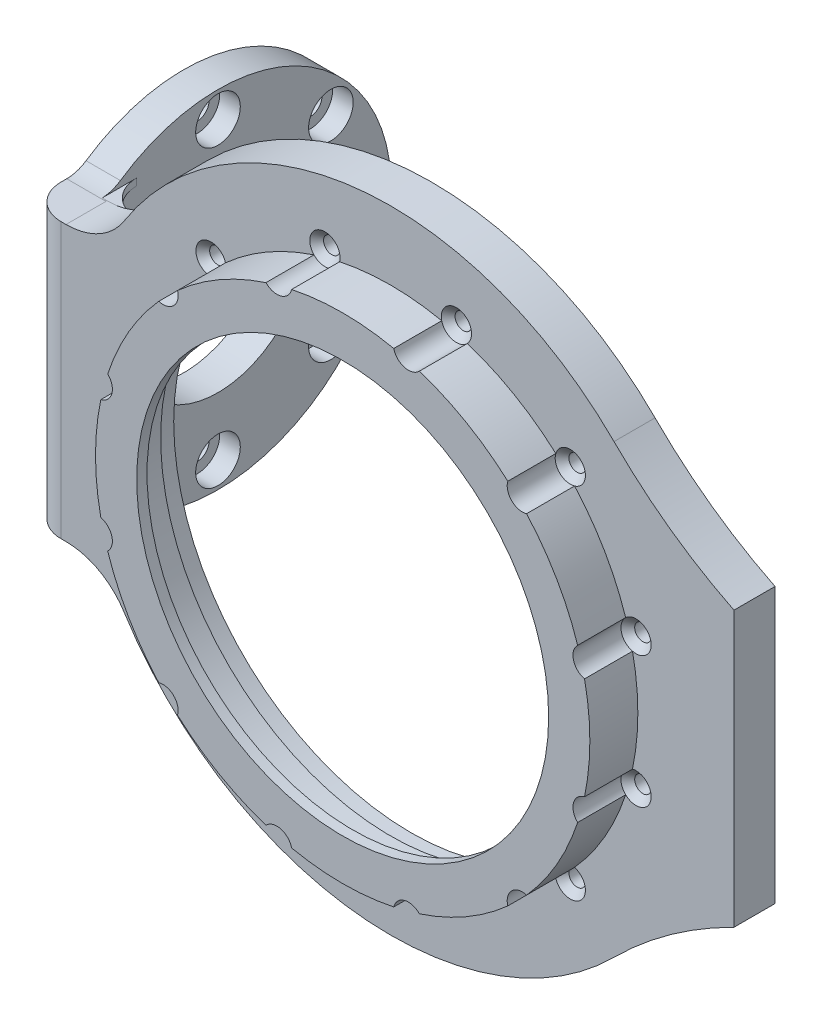
SolidWorks part; units mm, degrees
ref_plane "前视基准面" through (0, 0, 0) normal (0, 0, 1) x (1, 0, 0)
ref_plane "上视基准面" through (0, 0, 0) normal (0, 1, 0) x (1, 0, 0)
ref_plane "右视基准面" through (0, 0, 0) normal (1, 0, 0) x (0, 0, -1)
sketch "草图3" plane through (0, 0, 0) normal (0, 0, 1) x (1, 0, 0)
  circle A0 centre (0, 0) radius 34.6
  circle A1 centre (0, 0) radius 46
extrude "凸台-拉伸2" add sketch "草图3" along normal blind 3
ref_plane "基准面5" through (0, 0, 3) normal (0, 0, 1) x (1, 0, 0)
sketch "草图5" plane through (0, 0, 3) normal (0, 0, 1) x (1, 0, 0)
  circle A0 centre (0, 0) radius 33.5
  circle A1 centre (0, 0) radius 36
extrude "凸台-拉伸3" add sketch "草图5" along normal blind 5.49
sketch "草图2" plane through (0, 0, 0) normal (0, 0, 1) x (1, 0, 0)
  circle A0 centre (0, 0) radius 41.6
  circle A1 centre (0, 0) radius 46
extrude "凸台-拉伸1" add sketch "草图2" against normal blind 2.98
sketch "草图6" plane through (0, 0, 8.49) normal (0, 0, 1) x (1, 0, 0)
  circle A0 centre (0, 0) radius 30
  circle A1 centre (0, 0) radius 36
extrude "凸台-拉伸4" add sketch "草图6" along normal blind 1.5
sketch "草图8" plane through (0, 0, 0) normal (0, 0, 1) x (1, 0, 0)
  line L1 (-50, -20) -> (-50, 20)
  line L3 (50, -20) -> (50, 20)
  line L4 (-50, 20) -> (-41.4246, 20)
  line L5 (-50, -20) -> (-41.4246, -20)
  arc A5 (32.5269, 32.5269) -> (32.5269, -32.5269) centre (0, 0) cw
  arc A6 (50, -20) -> (32.5269, -32.5269) centre (79.2531, -79.2531) ccw
  arc A7 (50, 20) -> (32.5269, 32.5269) centre (79.2531, 79.2531) cw
  circle A8 centre (0, 0) radius 46 construction
  arc A9 (-41.4246, -20) -> (-41.4246, 20) centre (0, 0) cw
extrude "凸台-拉伸5" add sketch "草图8" along normal blind 3 and the other way blind 2.98
hole_wizard "M2 锥坑平头的锥孔1" positions "3D草图3" profile "草图12" countersink size "M2" standard "BSI" end condition through all
sketch3d "3D草图3"
  line L2 (0, 0, 0) -> (0, 37, 0)
  line L3 (0, 0, 0) -> (11.5811, 0, 0)
  point P55 (9.5763, 35.7393, 3)
  point P76 (26.163, 26.163, 3)
  point P83 (35.7393, 9.5763, 3)
  point P96 (-35.7393, 9.5763, 3)
  point P97 (-26.163, 26.163, 3)
  point P98 (-9.5763, 35.7393, 3)
  point P99 (35.7393, -9.5763, 3)
  point P100 (26.163, -26.163, 3)
  point P101 (9.5763, -35.7393, 3)
  point P102 (-9.5763, -35.7393, 3)
  point P103 (-26.163, -26.163, 3)
  point P104 (-35.7393, -9.5763, 3)
sketch "草图12" plane through (-35.7393, -9.5763, 3) normal (1, 0, 0) x (0, -1, 0)
  line L0 (0, 0) -> (0, 5.98)
  line L1 (0, 5.98) -> (1.2, 5.98)
  line L2 (1.2, 5.98) -> (1.2, 1)
  line L3 (1.2, 1) -> (2.2, 0)
  line L5 (2.2, 0) -> (0, 0)
  line L6 (-1.2, 1) -> (-2.2, 0) construction
  line L11 (0, -6.35) -> (0, 107.95) construction
  dimension "通孔孔直径" = 2.4
  dimension "通孔孔深度" = 5.98
  dimension "近端锥形沉头孔直径" = 4.4
  dimension "近端锥形沉头孔角度" = 90
sketch "草图13" plane through (0, 0, 3) normal (0, 0, 1) x (1, 0, 0)
  line L0 (0, 0) -> (0, 10.9464)
  line L1 (0, 0) -> (8.3109, 0)
  circle A0 centre (-35.7393, 9.5763) radius 2.2
  circle A1 centre (-26.163, 26.163) radius 2.2
  circle A2 centre (-9.5763, 35.7393) radius 2.2
  circle A3 centre (-9.5763, -35.7393) radius 2.2
  circle A4 centre (-26.163, -26.163) radius 2.2
  circle A5 centre (-35.7393, -9.5763) radius 2.2
  circle A6 centre (9.5763, -35.7393) radius 2.2
  circle A7 centre (26.163, -26.163) radius 2.2
  circle A8 centre (9.5763, 35.7393) radius 2.2
  circle A9 centre (26.163, 26.163) radius 2.2
  circle A10 centre (35.7393, -9.5763) radius 2.2
  circle A11 centre (35.7393, 9.5763) radius 2.2
extrude "切除-拉伸1" cut sketch "草图13" along normal up to next contours A5 | A4 | A0 | A1 | A2 | A9 | A11 | A10 | A6 | A3 | A8 | A7 region at (-35.7393, 9.5763, 3) region at (-26.163, 26.163, 3) region at (-9.5763, 35.7393, 3) region at (-9.5763, -35.7393, 3) region at (-26.163, -26.163, 3) region at (-35.7393, -9.5763, 3) region at (9.5763, -35.7393, 3) region at (26.163, 26.163, 3) region at (35.7393, -9.5763, 3) region at (35.7393, 9.5763, 3)
ref_plane "基准面6" through (-50, 0, 0) normal (-1, 0, 0) x (0, 0, 1)
sketch "草图14" plane through (-50, 0, 0) normal (-1, 0, 0) x (0, 0, 1)
  line L0 (-4.4369, 20) -> (3, 20)
  line L3 (3, 20) -> (3, -20)
  line L5 (-4.4369, -20) -> (3, -20)
  arc A1 (-4.4369, -20) -> (-4.4369, 20) centre (-19.85, 0) cw
extrude "凸台-拉伸6" add sketch "草图14" along normal blind 3 and the other way blind 2
fillet "圆角1" radius 10 1 edges at (-41.4246, 20, 0.01)
fillet "圆角2" radius 10 1 edges at (-41.4246, -20, 0.01)
fillet "圆角3" radius 5 1 edges at (-50.5, 20, -4.4369)
fillet "圆角4" radius 5 1 edges at (-53, 0, 3)
fillet "圆角5" radius 5 1 edges at (-50.5, -20, -4.4369)
ref_plane "基准面7" through (-48, -20.0026, -2.98) normal (0, 1, 0) x (1, 0, 0)
sketch "草图17" plane through (-48, -20.0026, -2.98) normal (0, 1, 0) x (1, 0, 0)
  line L0 (0, 0) -> (0, 5)
  line L1 (0, 2.6539) -> (0, 42.12) construction
  line L2 (0, 0) -> (5, 0)
  line L3 (9.1576, 0) -> (0.4856, 0) construction
  arc A1 (0, 5) -> (5, 0) centre (5, 5) ccw
extrude "凸台-拉伸7" add sketch "草图17" along normal blind 1
pattern_linear "阵列(线性)1" count 8 spacing 5.5722 along (0, 1, 0) skipping (1, 0), (6, 0) of "凸台-拉伸7"
sketch "草图18" plane through (0, 0, 3) normal (0, 0, 1) x (1, 0, 0)
  circle A0 centre (0, 0) radius 46
extrude "切除-拉伸2" cut sketch "草图18" against normal blind 2 from surface starting at face at (41.6, 0, -2.98)
sketch "草图19" plane through (-50, 0, 0) normal (-1, 0, 0) x (0, 0, 1)
  circle A1 centre (-19.85, 0) radius 13
extrude "切除-拉伸3" cut sketch "草图19" against normal through all and the other way through all contours A1
hole_wizard "M3 六角凹头盖的柱孔1" positions "3D草图4" profile "草图20" counterbore size "M3" standard "BSI" end condition up to next
sketch3d "3D草图4"
  point P0 (-48, 21.4664, -19.85)
  point P42 (-48, 13.7984, -36.2942)
  point P61 (-48, 13.7984, -3.4058)
  point P72 (-48, -13.7984, -36.2942)
  point P74 (-48, -21.4664, -19.85)
  point P76 (-48, -13.7984, -3.4058)
sketch "草图20" plane through (-48, 21.4664, -19.85) normal (0, 1, 0) x (0, 0, -1)
  line L0 (0, 0) -> (0, 5)
  line L1 (0, 5) -> (1.7, 5)
  line L3 (1.7, 5) -> (1.7, 3)
  line L4 (1.7, 3) -> (3.25, 3)
  line L5 (3.25, 3) -> (3.25, 0)
  line L7 (3.25, 0) -> (0, 0)
  line L11 (0, -6.35) -> (0, 107.95) construction
  dimension "通孔孔直径" = 3.4
  dimension "通孔孔深度" = 5
  dimension "柱形沉头孔直径" = 6.5
  dimension "柱形沉头孔深度" = 3
sketch "草图21" plane through (-50, 0, 0) normal (-1, 0, 0) x (0, 0, 1)
  circle A0 centre (-3.4058, 13.7984) radius 3.25
  circle A1 centre (-3.4058, -13.7984) radius 3.25
extrude "切除-拉伸4" cut sketch "草图21" against normal blind 15
